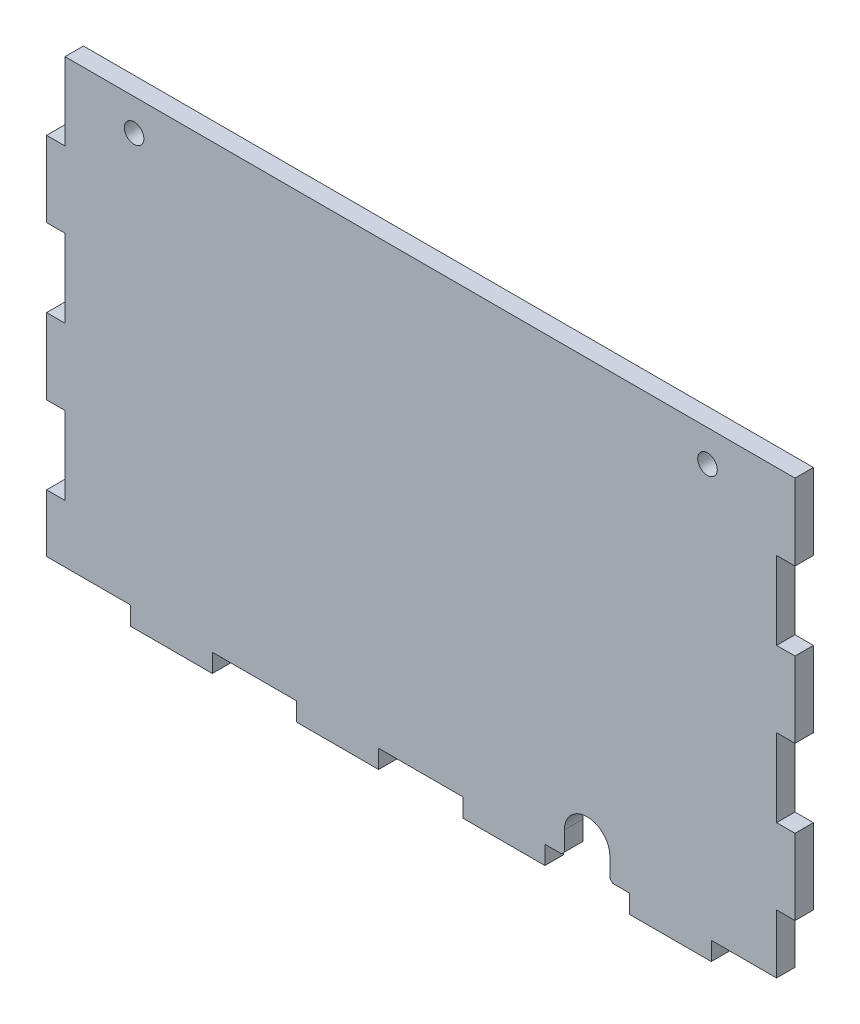
SolidWorks part; units mm, degrees
material "Acrylic (Medium-high impact)"
ref_plane "Front Plane" through (0, 0, 0) normal (0, 0, 1) x (1, 0, 0)
ref_plane "Top Plane" through (0, 0, 0) normal (0, 1, 0) x (1, 0, 0)
ref_plane "Right Plane" through (0, 0, 0) normal (1, 0, 0) x (0, 0, -1)
sketch "Sketch1" plane through (0, 0, 0) normal (0, 0, 1) x (1, 0, 0)
  line L1 (0, 0) -> (130, 0)
  line L2 (0, 0) -> (0, 80)
  line L3 (0, 80) -> (130, 80)
  line L4 (130, 0) -> (130, 80)
  dimension "D1" = 130
  dimension "D2" = 80
extrude "Boss-Extrude1" add sketch "Sketch1" along normal blind 3.2
sketch "Sketch2" plane through (0, 0, 3.2) normal (0, 0, 1) x (1, 0, 0)
  line L61 (14.4444, 3.2) -> (28.8889, 3.2) construction
  line L62 (0, 0) -> (14.4444, 0)
  line L67 (0, 0) -> (0, 3.2)
  line L72 (0, 3.2) -> (14.4444, 3.2)
  line L77 (14.4444, 0) -> (14.4444, 3.2)
  line L97 (28.8889, 0) -> (28.8889, 3.2)
  line L98 (28.8889, 0) -> (43.3333, 0)
  line L107 (43.3333, 0) -> (43.3333, 3.2)
  line L115 (28.8889, 3.2) -> (43.3333, 3.2)
  line L117 (43.3333, 3.2) -> (57.7778, 3.2) construction
  line L123 (57.7778, 0) -> (57.7778, 3.2)
  line L128 (57.7778, 0) -> (72.2222, 0)
  line L129 (72.2222, 0) -> (72.2222, 3.2)
  line L131 (57.7778, 3.2) -> (72.2222, 3.2)
  line L132 (72.2222, 3.2) -> (86.6667, 3.2) construction
  line L133 (86.6667, 0) -> (86.6667, 3.2)
  line L134 (86.6667, 0) -> (101.1111, 0)
  line L135 (101.1111, 0) -> (101.1111, 3.2)
  line L136 (86.6667, 3.2) -> (101.1111, 3.2)
  line L137 (101.1111, 3.2) -> (115.5556, 3.2) construction
  line L138 (115.5556, 0) -> (115.5556, 3.2)
  line L139 (115.5556, 0) -> (130, 0)
  line L142 (130, 0) -> (130, 80) construction
  line L143 (0, 80) -> (0, 0) construction
  line L144 (0, 13.3333) -> (3.2, 13.3333)
  line L145 (0, 13.3333) -> (0, 26.6667)
  line L146 (130, 3.2) -> (144.4444, 3.2) construction
  line L147 (0, 26.6667) -> (3.2, 26.6667)
  line L148 (3.2, 13.3333) -> (3.2, 26.6667)
  line L149 (3.2, 13.3333) -> (3.2, 0) construction
  line L150 (0, 40) -> (0, 53.3333)
  line L151 (0, 40) -> (3.2, 40)
  line L152 (3.2, 40) -> (3.2, 53.3333)
  line L153 (0, 53.3333) -> (3.2, 53.3333)
  line L154 (3.2, 40) -> (3.2, 26.6667) construction
  line L155 (0, 66.6667) -> (0, 80)
  line L156 (0, 66.6667) -> (3.2, 66.6667)
  line L157 (3.2, 66.6667) -> (3.2, 80)
  line L158 (0, 80) -> (3.2, 80)
  line L159 (3.2, 66.6667) -> (3.2, 53.3333) construction
  line L160 (130, 80) -> (0, 80) construction
  line L161 (126.8, 80) -> (126.8, 66.6667) construction
  line L162 (126.8, 40) -> (126.8, 26.6667)
  line L163 (126.8, 66.6667) -> (130, 66.6667)
  line L164 (126.8, 66.6667) -> (126.8, 53.3333)
  line L165 (126.8, 53.3333) -> (130, 53.3333)
  line L166 (130, 66.6667) -> (130, 53.3333)
  line L167 (126.8, 40) -> (130, 40)
  line L168 (130, 40) -> (130, 26.6667)
  line L169 (126.8, 26.6667) -> (130, 26.6667)
  line L170 (126.8, 53.3333) -> (126.8, 40) construction
  line L172 (126.8, 13.3333) -> (130, 13.3333)
  line L173 (130, 13.3333) -> (130, 0)
  line L175 (126.8, 26.6667) -> (126.8, 13.3333) construction
  line L183 (115.5556, 3.2) -> (130, 3.2) [skipped]
  line L184 (130, 0) -> (130, 3.2) [skipped]
  line L185 (126.8, 13.3333) -> (126.8, 3.2)
  line L186 (126.8, 3.2) -> (115.5556, 3.2)
  line L187 (126.8, 0) -> (130, 0) [skipped]
  line L188 (126.8, 13.3333) -> (126.8, 0) [skipped]
  dimension "D2" = 3.2
  dimension "D4" = 3.2
  dimension "D6" = 3.2
  dimension "D1" = 5
  dimension "D3" = 3
  dimension "D5" = 3
extrude "Cut-Extrude1" cut sketch "Sketch2" against normal through all
sketch "Sketch3" plane through (0, 0, 3.2) normal (0, 0, 1) x (1, 0, 0)
  line L0 (0, 66.6667) -> (0, 53.3333) construction
  line L1 (130, 80) -> (3.2, 80) construction
  line L2 (0, 66.6667) -> (130, 66.6667) construction
  line L3 (65, 66.6667) -> (65, 50066.6667) construction
  circle A0 centre (15.2, 74.5) radius 1.7
  circle A1 centre (114.8, 74.5) radius 1.7
  point P10 (65, 66.6667)
  dimension "D1" = 3.4
  dimension "D2" = 15.2
  dimension "D3" = 5.5
extrude "Cut-Extrude2" cut sketch "Sketch3" against normal up to next
sketch "Sketch4" plane through (0, 0, 0) normal (0, 0, -1) x (-1, 0, 0)
  line L0 (-97.8389, 3.2) -> (-97.8389, 7.05)
  line L1 (-101.1111, 3.2) -> (-86.6667, 3.2) construction
  line L2 (-89.9389, 3.2) -> (-89.9389, 7.05)
  line L3 (-97.8389, 3.2) -> (-89.9389, 3.2)
  line L4 (-101.1111, 0) -> (-86.6667, 0) construction
  line L5 (-101.1111, 0) -> (-115.5556, 0) construction
  line L6 (-101.1111, 0) -> (-101.1111, 3.2) construction
  line L7 (-72.2222, 0) -> (-86.6667, 0) construction
  arc A0 (-97.8389, 7.05) -> (-89.9389, 7.05) centre (-93.8889, 7.05) cw
  point P15 (-93.8889, 0)
  dimension "D2" = 7.8
  dimension "D1" = 7.9
extrude "Cut-Extrude3" cut sketch "Sketch4" against normal up to next
chamfer "Chamfer1" distance 0.5 angle 45 2 edges at (89.9389, 3.2, 1.6) (97.8389, 3.2, 1.6)
other "Width tolerance" flip direction yes face at (1.6, 53.3333, 1.6) face at (1.6, 26.6667, 1.6) face at (1.6, 13.3333, 1.6) face at (1.6, 40, 1.6) face at (1.6, 66.6667, 1.6) face at (14.4444, 1.6, 1.6) face at (43.3333, 1.6, 1.6) face at (72.2222, 1.6, 1.6) face at (101.1111, 1.6, 1.6) face at (28.8889, 1.6, 1.6) face at (57.7778, 1.6, 1.6) face at (86.6667, 1.6, 1.6) face at (115.5556, 1.6, 1.6) face at (128.4, 13.3333, 1.6) face at (128.4, 66.6667, 1.6) face at (128.4, 40, 1.6) face at (128.4, 26.6667, 1.6) face at (128.4, 53.3333, 1.6) offset 0.1 parameters "D1"=0.1
equation "\"wall_thickness\"= 3.2mm"
equation "\"D1@Boss-Extrude1\"=\"wall_thickness\""
equation "\"slot_width_tolerance\"= 0.1mm"
equation "\"slot_depth\"= 3.2mm"
equation "\"D2@Sketch2\"=\"slot_depth\""
equation "\"D4@Sketch2\"=\"slot_depth\""
equation "\"D6@Sketch2\"=\"slot_depth\""
equation "\"D2@Sketch3\"=12.00mm+\"slot_depth\""
equation "\"D1@Width tolerance\"=\"slot_width_tolerance\""
